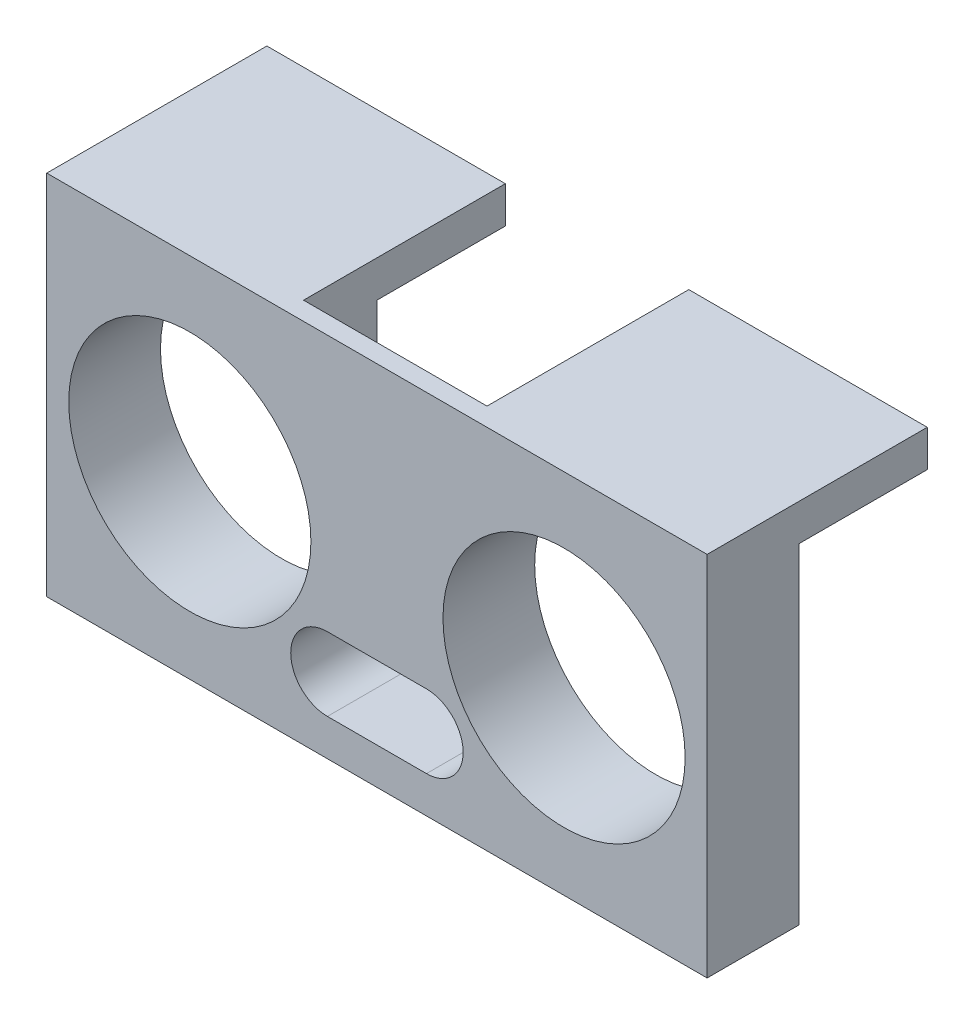
SolidWorks part; units mm, degrees
ref_plane "Front Plane" through (0, 0, 0) normal (0, 0, 1) x (1, 0, 0)
ref_plane "Top Plane" through (0, 0, 0) normal (0, 1, 0) x (1, 0, 0)
ref_plane "Right Plane" through (0, 0, 0) normal (1, 0, 0) x (0, 0, -1)
sketch "Sketch1" plane through (0, 0, 0) normal (0, 0, 1) x (1, 0, 0)
  line L0 (0.239, 22.646) -> (45.489, 22.646) construction
  line L1 (0, 0) -> (45.72, 0)
  line L2 (0, 0) -> (0, 22.86)
  line L3 (0, 22.86) -> (45.72, 22.86)
  line L4 (45.72, 0) -> (45.72, 22.86)
  line L5 (45.489, 2.246) -> (0.239, 2.246) construction
  line L6 (0.239, 2.246) -> (0.239, 22.646) construction
  line L7 (45.489, 22.646) -> (45.489, 2.246) construction
  line L8 (19.431, 5.08) -> (26.289, 5.08) construction
  line L9 (19.431, 7.62) -> (26.289, 7.62)
  line L10 (19.431, 2.54) -> (26.289, 2.54)
  line L11 (26.059, 7.306) -> (19.669, 7.306) construction
  line L12 (19.669, 2.996) -> (26.059, 2.996) construction
  line L13 (19.669, 6.856) -> (19.669, 6.656) construction
  circle A0 centre (9.906, 12.446) radius 8.382
  circle A1 centre (35.814, 12.446) radius 8.382
  circle A4 centre (9.914, 12.446) radius 7.75 construction
  arc A5 (19.431, 7.62) -> (19.431, 2.54) centre (19.431, 5.08) ccw
  arc A6 (26.289, 2.54) -> (26.289, 7.62) centre (26.289, 5.08) ccw
  circle A7 centre (25.703, 5.246) radius 0.25 construction
  point P9 (22.86, 5.08)
  dimension "D1" = 22.86
  dimension "D3" = 16.764
  dimension "D5" = 10.414
  dimension "D6" = 9.675
  dimension "D15" = 17.4
  dimension "D2" = 45.72
  dimension "D4" = 20.4
  dimension "D7" = 9.906
  dimension "D8" = 9.906
  dimension "D9" = 45.25
  dimension "D10" = 4.31
  dimension "D11" = 5.08
  dimension "D12" = 6.39
  dimension "D13" = 6.858
  dimension "D14" = 22.86
  dimension "D16" = 17.78
extrude "Boss-Extrude1" add sketch "Sketch1" along normal blind 6.35
sketch "Sketch2" plane through (0, 0, 0) normal (0, 0, -1) x (-1, 0, 0)
  line L0 (-45.72, 22.86) -> (0, 22.86) construction
  line L1 (-29.21, 22.86) -> (-16.51, 22.86)
  line L2 (-29.21, 22.86) -> (-29.21, 19.05)
  line L3 (-29.21, 19.05) -> (-16.51, 19.05)
  line L4 (-16.51, 22.86) -> (-16.51, 19.05)
  point P6 (-19.3369, 25.4)
  point P7 (-22.86, 22.86)
  point P8 (-22.86, 22.86)
  dimension "D1" = 12.7
  dimension "D2" = 3.81
  dimension "D3" = 0
extrude "Cut-Extrude1" cut sketch "Sketch2" against normal blind 5.08
sketch "Sketch3" plane through (0, 22.86, 0) normal (0, 1, 0) x (1, 0, 0)
  line L0 (0, -6.35) -> (0, 8.89)
  line L1 (0, 8.89) -> (16.51, 8.89)
  line L2 (16.51, 8.89) -> (16.51, -5.08)
  line L3 (16.51, -5.08) -> (29.21, -5.08)
  line L4 (29.21, -5.08) -> (29.21, 8.89)
  line L5 (29.21, 8.89) -> (45.72, 8.89)
  line L6 (45.72, 8.89) -> (45.72, -6.35)
  line L7 (45.72, -6.35) -> (0, -6.35)
  point P11 (0, 0)
  dimension "D1" = 15.24
extrude "Boss-Extrude2" add sketch "Sketch3" along normal blind 2.54 contours L1 L2 L3 L4 L5 L6 L7 L0
